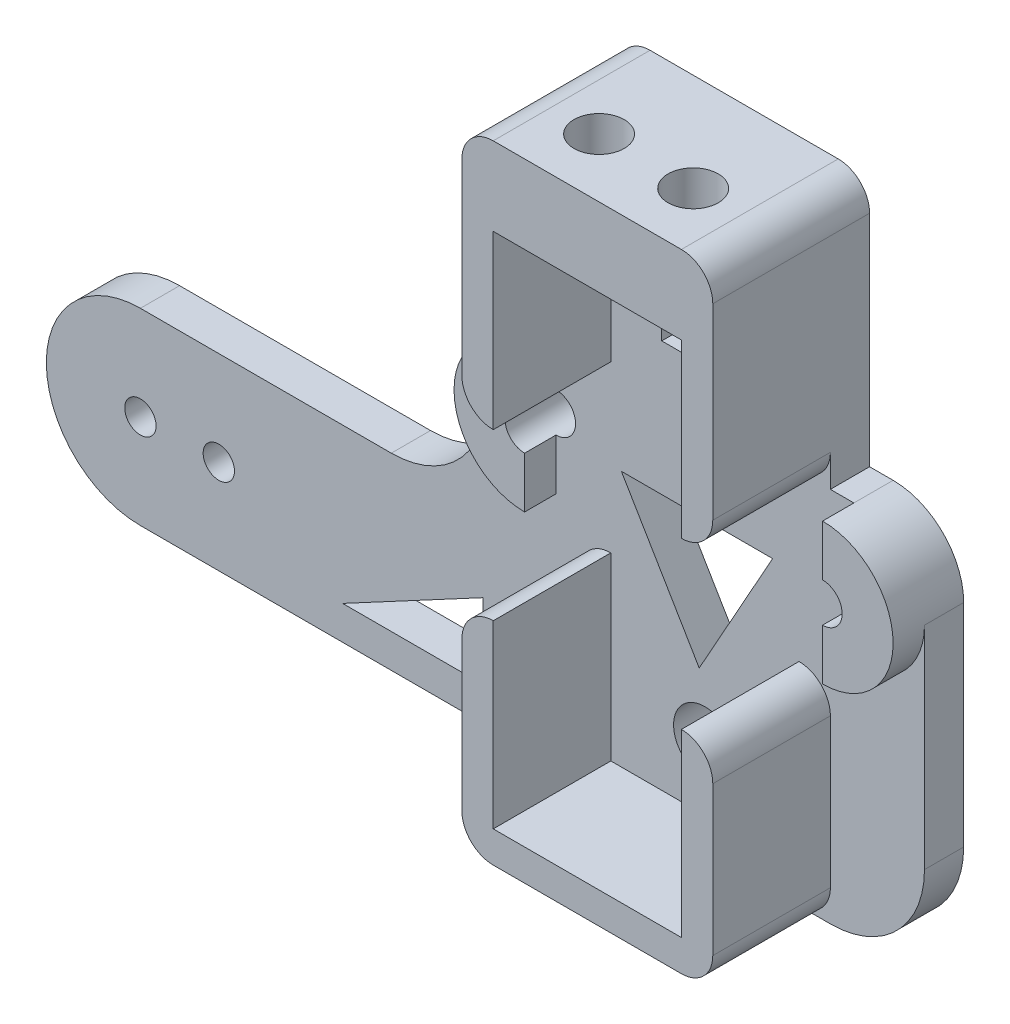
SolidWorks part; units mm, degrees
ref_plane "前视基准面" through (0, 0, 0) normal (0, 0, 1) x (1, 0, 0)
ref_plane "上视基准面" through (0, 0, 0) normal (0, 1, 0) x (1, 0, 0)
ref_plane "右视基准面" through (0, 0, 0) normal (1, 0, 0) x (0, 0, -1)
other "Configuration Table"
sketch "草图1" plane through (0, 0, 0) normal (0, 0, 1) x (1, 0, 0)
  line L0 (0, 0) -> (36, 0) construction
  line L1 (0, 6) -> (28, 6)
  line L2 (0, -6) -> (44, -6)
  line L3 (44, -6) -> (44, 18)
  line L4 (44, 18) -> (28, 18)
  line L6 (42, -4) -> (30, -4)
  line L7 (30, -4) -> (30, 9)
  line L8 (30, 9) -> (28, 9)
  line L9 (28, 9) -> (28, -6)
  line L10 (42, -4) -> (42, 9)
  line L11 (42, 9) -> (44, 9)
  line L12 (28, 18) -> (28, 9)
  line L13 (28, 18) -> (26.5, 18)
  line L14 (28, 9) -> (26.5, 9)
  line L15 (26.5, 18) -> (26.5, 9)
  line L16 (36, 0) -> (36, 13.2517) construction
  line L17 (45.5, 18) -> (45.5, 9)
  line L18 (44, 18) -> (45.5, 18)
  line L19 (44, 9) -> (45.5, 9)
  line L20 (22, 13.5) -> (22, 6)
  line L21 (50, 13.5) -> (50, -6)
  line L22 (50, -6) -> (44, -6)
  arc A0 (0, 6) -> (0, -6) centre (0, 0) ccw
  circle A2 centre (0, 0) radius 1
  circle A3 centre (36, 0) radius 2
  arc A5 (26.5, 18) -> (26.5, 9) centre (26.5, 13.5) ccw
  arc A6 (45.5, 18) -> (45.5, 9) centre (45.5, 13.5) cw
  circle A7 centre (26.5, 13.5) radius 1.25
  circle A8 centre (45.5, 13.5) radius 1.25
  circle A9 centre (5, 0) radius 1
  point P3 (18, 0)
  point P23 (29, 9)
  dimension "D1" = 2
  dimension "D2" = 4
  dimension "D4" = 6
  dimension "D5" = 6
  dimension "D13" = 2.5
  dimension "D14" = 2
  dimension "D15" = 5
  dimension "D3" = 36
  dimension "D6" = 6
  dimension "D7" = 2
  dimension "D8" = 2
  dimension "D9" = 2
  dimension "D10" = 13
  dimension "D11" = 9
  dimension "D12" = 1.5
extrude "凸台-拉伸1" add sketch "草图1" along normal blind 2.5 contours L1 A0 L2 L9 A2 | L11 L10 L6 L7 L8 L9 L2 L3 | A7 L15 L14 L12 L13 | A7 L15 A5 | L17 A8 A6 | L17 A8 L18 L3 L19 | L4 L12 L8 L7 L6 L10 L11 L3 A3 | A5 L20 L1 L9 L14 | L21 A6 L19 L3 L22 region at (11.7647, 0, 0) region at (24.6121, 7.9872, 0) region at (28.2193, 7.5, 0) region at (24.4748, 13.5, 0) region at (36, 8.1201, 0) region at (27.25, 9.0912, 0) region at (47.0919, 1.8918, 0) region at (44.0912, 13.5, 0) region at (47.5252, 13.5, 0)
extrude "凸台-拉伸2" add sketch "草图1<3>" along normal blind 10 contours L11 L10 L6 L7 L8 L9 L2 L3 region at (28.2193, 7.5, 0)
sketch "草图1<3>" plane through (0, 0, 0) normal (0, 0, 1) x (1, 0, 0) same geometry as "草图1"
extrude "凸台-拉伸4" add sketch "草图1<5>" along normal blind 2 from surface contours A7 L15 A5 | L17 A8 A6 region at (24.4748, 13.5, 0) region at (47.5252, 13.5, 0) starting at face at (46.75, 13.5, 2.5)
sketch "草图1<5>" plane through (0, 0, 0) normal (0, 0, 1) x (1, 0, 0) same geometry as "草图1"
fillet "圆角1" radius 1 2 edges at (42, 9, 6.25) (30, 9, 6.25)
fillet "圆角2" radius 6 2 edges at (50, -6, 1.25) (22, 6, 1.25)
sketch "草图2" plane through (0, 0, 2.5) normal (0, 0, 1) x (1, 0, 0)
  line L0 (28, -6) -> (28, 34)
  line L1 (28, 34) -> (44, 34)
  line L2 (44, 34) -> (44, -6)
  line L3 (30, -4) -> (30, 34)
  line L4 (42, 8) -> (42, 34)
  line L8 (44, 9) -> (43, 9)
  line L9 (42, 8) -> (42, -4)
  line L10 (42, -4) -> (30, -4)
  line L11 (30, -4) -> (30, 8)
  line L12 (29, 9) -> (28, 9)
  line L13 (28, 9) -> (28, -6)
  line L14 (28, -6) -> (44, -6)
  line L15 (44, -6) -> (44, 9)
  line L16 (44, 9) -> (43, 9)
  line L17 (42, 8) -> (42, -4)
  line L18 (42, -4) -> (30, -4)
  line L19 (30, -4) -> (30, 8)
  line L20 (29, 9) -> (28, 9)
  line L21 (28, 9) -> (28, -6)
  line L22 (28, -6) -> (44, -6)
  line L23 (44, -6) -> (44, 9)
  arc A2 (43, 9) -> (42, 8) centre (43, 8) ccw
  arc A3 (30, 8) -> (29, 9) centre (29, 8) ccw
  arc A4 (43, 9) -> (42, 8) centre (43, 8) ccw
  arc A5 (30, 8) -> (29, 9) centre (29, 8) ccw
  line M19 (45.5, 18) -> (26.5, 18)
  line M30 (28, 9) -> (29, 9)
  arc M31 (29, 9) -> (30, 8) centre (29, 8) cw
  arc M35 (42, 8) -> (43, 9) centre (43, 8) cw
  line M36 (43, 9) -> (44, 9)
  dimension "D2" = 40
  dimension "D1" = 0
extrude "凸台-拉伸5" add sketch "草图2" along normal up to surface (7.5 mm away) contours L4 L2 L1 M19 | L4 L2 M35 M36 M19 | L3 L0 M31 M19 M30 | L3 L1 L0 M19 region at (29.0092, 13.4443, 2.5) region at (29, 26, 2.5) region at (42.9908, 13.4443, 2.5) region at (43, 26, 2.5) up to face at (36, 3.2414, 10)
sketch "草图3" plane through (28, 0, 0) normal (-1, 0, 0) x (0, 0, 1)
  line L0 (2.5, 29) -> (10, 29)
  line L1 (2.5, 18) -> (2.5, 34) construction
  line L2 (10, 34) -> (10, -6) construction
  line L3 (10, -6) -> (2.5, -6) construction
  line L4 (2.5, 29) -> (2.5, 34)
  line L5 (2.5, 34) -> (10, 34)
  line L6 (10, 34) -> (10, 29)
  dimension "D1" = 35
extrude "凸台-拉伸6" add sketch "草图3" against normal up to surface (14 mm away) up to face at (42, 15.6, 5.5)
sketch "草图4" plane through (0, 34, 0) normal (0, 1, 0) x (1, 0, 0)
  line L0 (28, -10) -> (28, -2.5) construction
  line L1 (44, -10) -> (44, -2.5) construction
  circle A0 centre (33, -6.25) radius 1.6
  circle A1 centre (39, -6.25) radius 1.6
  point P8 (0, 0)
  dimension "D1" = 3.2
  dimension "D2" = 3.2
  dimension "D3" = 5
  dimension "D4" = 5
extrude "切除-拉伸1" cut sketch "草图4" against normal blind 10
sketch "草图5" plane through (0, 0, 0) normal (0, 0, -1) x (-1, 0, 0)
  line L3 (-30.6707, 12.3355) -> (-40.3177, 12.3355)
  line L4 (-40.3177, 12.3355) -> (-35.6346, 3.9504)
  line L5 (-35.6346, 3.9504) -> (-30.6707, 12.3355)
  point P2 (-30.6707, 12.3355)
  point P4 (-35.6346, 3.9504)
extrude "切除-拉伸2" cut sketch "草图5" against normal blind 10
sketch "草图6" plane through (0, 0, 0) normal (0, 0, -1) x (-1, 0, 0)
  line L0 (-21.8612, 0.9493) -> (-21.8612, -3.8505)
  line L1 (-21.8612, -3.8505) -> (-12.8962, -3.8505)
  line L2 (-12.8962, -3.8505) -> (-21.8612, 0.9493)
extrude "切除-拉伸3" cut sketch "草图6" against normal blind 10
sketch "草图7" plane through (0, 18, 0) normal (0, 1, 0) x (1, 0, 0)
  line L1 (28, -2.5) -> (44, -2.5)
  line L2 (28, -2.5) -> (28, 0)
  line L3 (28, 0) -> (44, 0)
  line L4 (44, -2.5) -> (44, 0)
extrude "凸台-拉伸7" add sketch "草图7" along normal up to surface (16 mm away) up to face at (33, 34, 7.85)
sketch "草图8" plane through (0, 0, 10) normal (0, 0, 1) x (1, 0, 0)
  line L0 (28, 34) -> (28, -6) construction
  line L1 (28, 18.0461) -> (44, 18.0461)
  line L2 (28, 18.0461) -> (28, 7.4945)
  line L3 (28, 7.4945) -> (44, 7.4945)
  line L4 (44, 18.0461) -> (44, 7.4945)
  line L5 (44, 18) -> (44, -6) construction
extrude "切除-拉伸4" cut sketch "草图8" against normal up to surface (7.5 mm away) up to face at (18.8729, -2.2506, 2.5)
sketch "草图9" plane through (0, 0, 2.5) normal (0, 0, 1) x (1, 0, 0)
  line L0 (33.2458, 27.7373) -> (33.2458, 20.8229)
  line L1 (33.2458, 20.8229) -> (40.2323, 20.8229)
  line L2 (40.2323, 20.8229) -> (33.2458, 27.7373)
extrude "切除-拉伸5" cut sketch "草图9" against normal blind 10 contours L1 L2 L0 region at (35.5746, 23.1277, 2.5)
fillet "圆角3" radius 2 8 edges at (44, 7.4945, 6.25) (28, 7.4945, 6.25) (28, 18.0461, 6.25) (44, 18.0461, 6.25) (44, -6, 6.25) (28, -6, 6.25) (44, 34, 5) (28, 34, 5)
